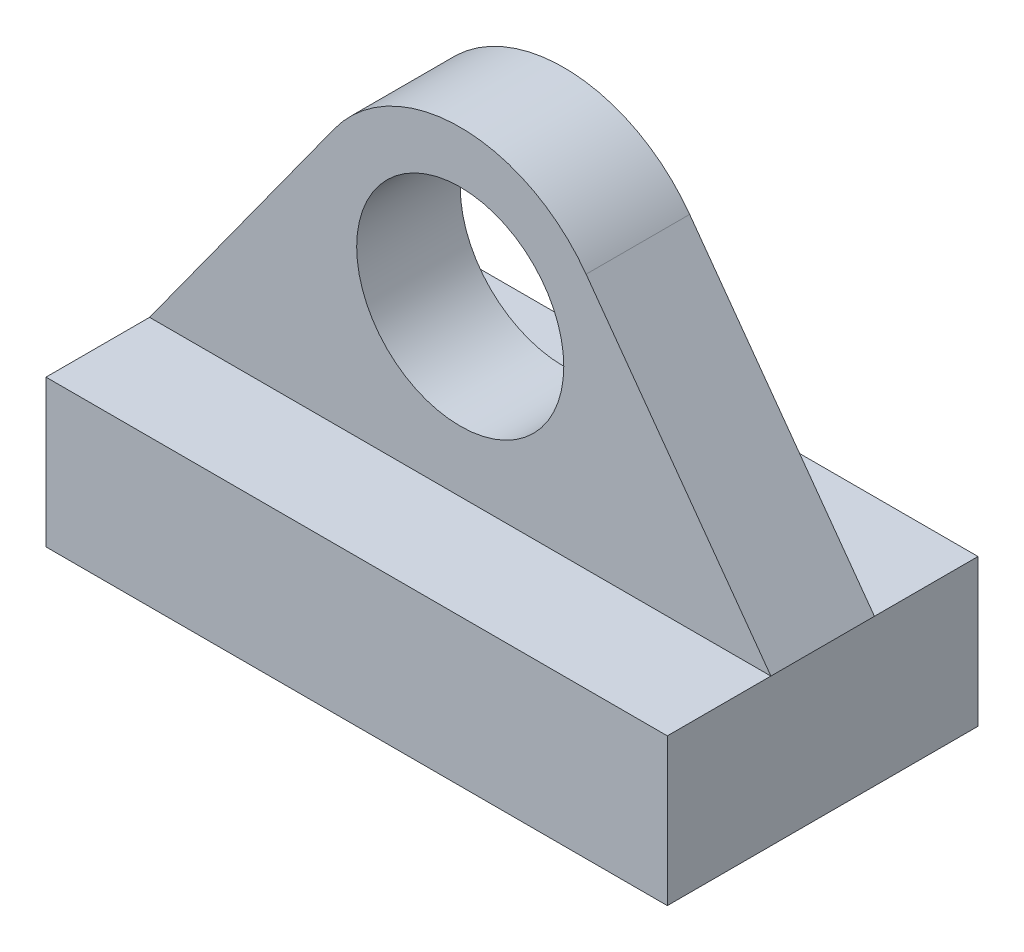
SolidWorks part; units mm, degrees
ref_plane "Front Plane" through (0, 0, 0) normal (0, 0, 1) x (1, 0, 0)
ref_plane "Top Plane" through (0, 0, 0) normal (0, 1, 0) x (1, 0, 0)
ref_plane "Right Plane" through (0, 0, 0) normal (1, 0, 0) x (0, 0, -1)
sketch "Sketch1" plane through (0, 0, 0) normal (0, 0, 1) x (1, 0, 0)
  line L1 (-19.05, -4.5085) -> (19.05, -4.5085)
  line L2 (-19.05, -4.5085) -> (-19.05, 4.5085)
  line L3 (-19.05, 4.5085) -> (19.05, 4.5085)
  line L4 (19.05, -4.5085) -> (19.05, 4.5085)
  line L5 (-19.05, -4.5085) -> (19.05, 4.5085) construction
  line L6 (-19.05, 4.5085) -> (19.05, -4.5085) construction
  point P0 (0, 0)
  dimension "D1" = 38.1
  dimension "D2" = 9.017
extrude "Boss-Extrude1" add sketch "Sketch1" along normal mid plane 19.05
sketch "Sketch2" plane through (0, 0, 0) normal (0, 0, 1) x (1, 0, 0)
  line L0 (-19.05, 4.5085) -> (-7.7197, 20.1846)
  line L1 (0, 0) -> (0, 14.605) construction
  line L2 (19.05, 4.5085) -> (7.7197, 20.1846)
  line L4 (-19.05, 4.5085) -> (19.05, 4.5085)
  arc A0 (7.7197, 20.1846) -> (-7.7197, 20.1846) centre (0, 14.605) ccw
  circle A1 centre (0, 14.605) radius 6.35
  dimension "D2" = 19.05
  dimension "D3" = 12.7
  dimension "D1" = 14.605
extrude "Boss-Extrude2" add sketch "Sketch2" along normal mid plane 6.35
